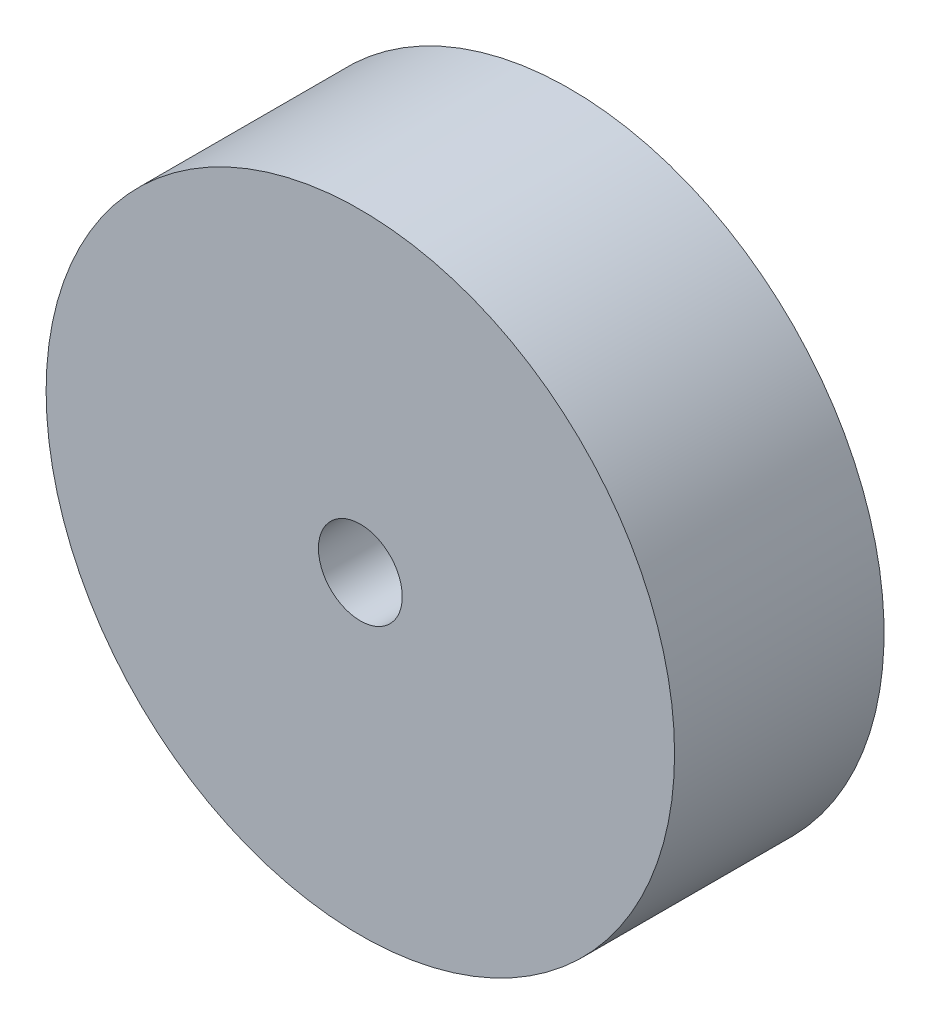
SolidWorks part; units mm, degrees
ref_plane "前视基准面" through (0, 0, 0) normal (0, 0, 1) x (1, 0, 0)
ref_plane "上视基准面" through (0, 0, 0) normal (0, 1, 0) x (1, 0, 0)
ref_plane "右视基准面" through (0, 0, 0) normal (1, 0, 0) x (0, 0, -1)
sketch "草图1" plane through (0, 0, 0) normal (0, 0, 1) x (1, 0, 0)
  circle A0 centre (0, -10) radius 30
  dimension "D1" = 60
extrude "凸台-拉伸1" add sketch "草图1" along normal blind 10
sketch "草图2" plane through (0, 0, 0) normal (0, 0, -1) x (-1, 0, 0)
  line L0 (28.2843, 0) -> (-28.2843, 0)
  line L1 (28.2843, -20) -> (-28.2843, -20)
  arc A0 (28.2843, 0) -> (-28.2843, 0) centre (0, -10) ccw
  arc A1 (-28.2843, -20) -> (28.2843, -20) centre (0, -10) ccw
extrude "凸台-拉伸2" add sketch "草图2" along normal blind 10
sketch "草图3" plane through (0, 0, -10) normal (0, 0, -1) x (-1, 0, 0)
  line L0 (25, 0) -> (25, -20)
  line L1 (25, -20) -> (28.2843, -20)
  line L2 (25, 0) -> (28.2843, 0)
  line L3 (-28.2843, 0) -> (-25, 0)
  line L4 (-25, 0) -> (-25, -20)
  line L5 (-25, -20) -> (-28.2843, -20)
  circle A0 centre (0, -10) radius 30
  line M3 (28.2843, -20) -> (-28.2843, -20)
extrude "凸台-拉伸3" add sketch "草图3" against normal up to surface (10 mm away) contours L3 A0 L4 M3 | A0 L2 L0 M3 region at (-27.2466, -10, -10) region at (27.2466, -10, -10) up to face at (0, -10, 0)
sketch "草图4" plane through (0, 0, 0) normal (0, 0, -1) x (-1, 0, 0)
  line L0 (25, -20) -> (-25, -20) construction
  line L1 (25.5, 0.1) -> (-25.5, 0.1)
  line L2 (25.5, 0.1) -> (25.5, -20.1)
  line L3 (25.5, -20.1) -> (-25.5, -20.1)
  line L4 (-25.5, 0.1) -> (-25.5, -20.1)
  line L5 (25.5, 0.1) -> (-25.5, -20.1) construction
  line L6 (25.5, -20.1) -> (-25.5, 0.1) construction
  line L7 (-25, 0) -> (-25, -20) construction
  point P0 (0, -10)
  dimension "D1" = 0.1
  dimension "D2" = 0.5
extrude "切除-拉伸1" cut sketch "草图4" along normal blind 22
sketch "草图5" plane through (0, -20.1, 0) normal (0, 1, 0) x (1, 0, 0)
  line L0 (-33.7868, 3) -> (34.3638, 3) construction
  line L1 (-25.5, 10) -> (25.5, 10) construction
  circle A2 centre (0, 3) radius 1.45
  dimension "D6" = 2.9
  dimension "D1" = 7
extrude "切除-拉伸2" cut sketch "草图5" against normal blind 29 and the other way blind 38
sketch "草图8" plane through (0, 0, 0) normal (0, 0, -1) x (-1, 0, 0)
  circle A0 centre (0, -10) radius 4
  dimension "D1" = 8
extrude "切除-拉伸5" cut sketch "草图8" against normal blind 57
